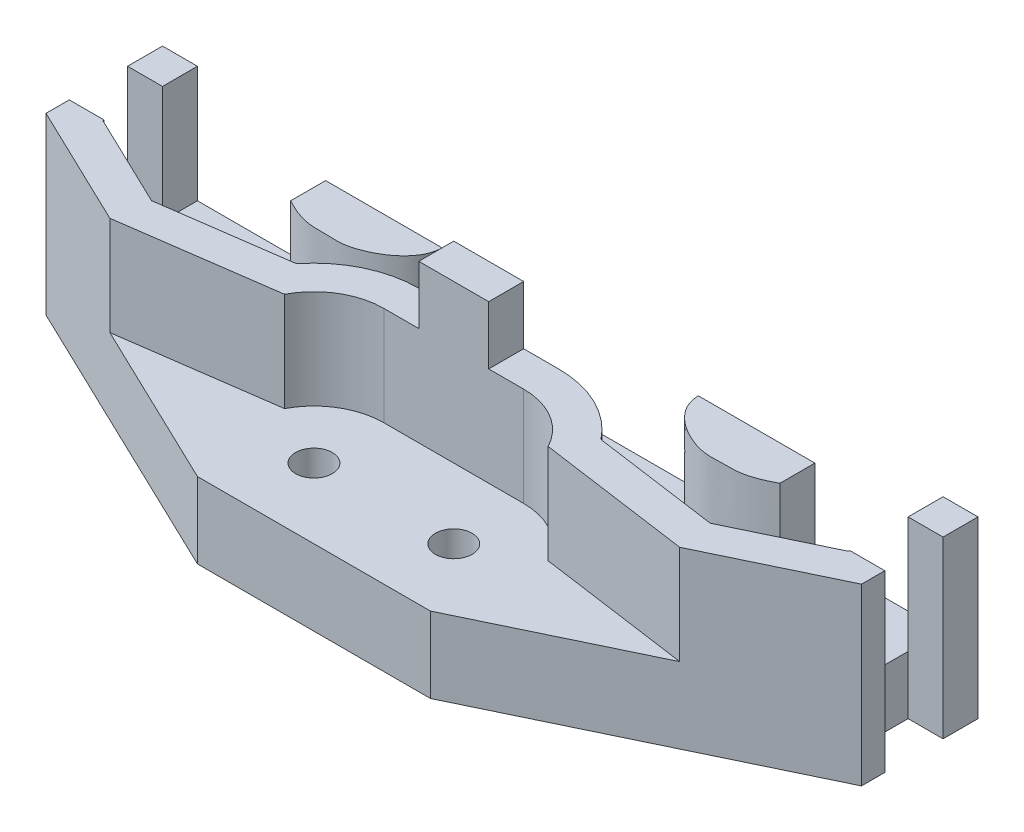
SolidWorks part; units mm, degrees
ref_plane "Front Plane" through (0, 0, 0) normal (0, 0, 1) x (1, 0, 0)
ref_plane "Top Plane" through (0, 0, 0) normal (0, 1, 0) x (1, 0, 0)
ref_plane "Right Plane" through (0, 0, 0) normal (1, 0, 0) x (0, 0, -1)
sketch "Sketch1" plane through (0, 0, 0) normal (0, 1, 0) x (1, 0, 0)
  line L0 (0, 0) -> (20, 0)
  line L1 (10, 0) -> (10, 12) construction
  line L2 (10, 12) -> (-25, 12) construction
  line L3 (0, 0) -> (-25, 12)
  line L4 (-25, 12) -> (-25, 22)
  line L5 (-25, 22) -> (45, 22)
  line L6 (45, 22) -> (45, 12)
  line L7 (45, 12) -> (20, 0)
  dimension "D1" = 35
  dimension "D2" = 20
  dimension "D3" = 12
  dimension "D4" = 70
  dimension "D5" = 10
  dimension "D6" = 10
extrude "Boss-Extrude1" add sketch "Sketch1" along normal blind 5
ref_plane "Plane1" through (10, 0, 0) normal (1, 0, 0) x (0, 0, -1)
sketch "Sketch2" plane through (0, 5, 0) normal (0, 1, 0) x (1, 0, 0)
  line L0 (10, 0) -> (10, 22) construction
  line L1 (0, 0) -> (20, 0) construction
  line L2 (45, 22) -> (-25, 22) construction
  circle A0 centre (4, 6) radius 1.575
  circle A1 centre (16, 6) radius 1.575
  dimension "D1" = 3.15
  dimension "D2" = 6
  dimension "D3" = 6
extrude "Cut-Extrude1" cut sketch "Sketch2" against normal blind 3
sketch "Sketch3" plane through (0, 5, 0) normal (0, 1, 0) x (1, 0, 0)
  line L0 (4, 6) -> (-8.7631, 4.2063) construction
  line L1 (-25, 12) -> (0, 0) construction
  line L2 (-8.7631, 4.2063) -> (-8.7631, 22) construction
  line L3 (45, 22) -> (-25, 22) construction
  line L4 (-2.3815, 5.1031) -> (-2.8686, 8.5691) construction
  line L5 (-2.8686, 8.5691) -> (4.0027, 9.5348) construction
  line L6 (-1.3131, 8.7877) -> (-14.4587, 6.9402)
  line L7 (10, 0) -> (10, 22) construction
  line L8 (0, 0) -> (20, 0) construction
  line L10 (-14.4587, 6.9402) -> (-25, 12)
  line L11 (-25, 12) -> (-25, 22)
  line L12 (-25, 22) -> (-22, 22)
  line L13 (-21.9703, 13.8734) -> (-25, 15.3277) construction
  line L14 (-21.9703, 13.8734) -> (-9.0961, 7.6939) construction
  line L15 (-19.7294, 9.4701) -> (-13.715, 22) construction
  line L17 (-3.069, 11.5704) -> (-13.9782, 10.0372)
  line L19 (-7.8859, 7.8639) -> (-9.8726, 22) construction
  line L21 (4, 12) -> (4, 15) construction
  line L30 (-22, 22) -> (-22, 13.8877)
  line L32 (0.4296, 9.0326) -> (0.012, 12.0034) construction
  line L33 (0.012, 12.0034) -> (-19.3407, 9.2836) construction
  line L34 (-22, 13.8877) -> (-13.9782, 10.0372)
  line L35 (4, 15) -> (16, 15)
  line L36 (4, 12) -> (16, 12)
  line L37 (21.3131, 8.7877) -> (34.4587, 6.9402)
  line L38 (34.4587, 6.9402) -> (45, 12)
  line L39 (45, 12) -> (45, 22)
  line L40 (45, 22) -> (42, 22)
  line L41 (42, 22) -> (42, 13.8877)
  line L42 (42, 13.8877) -> (33.9782, 10.0372)
  line L43 (23.069, 11.5704) -> (33.9782, 10.0372)
  arc A0 (-1.3131, 8.7877) -> (4, 12) centre (4, 6) cw
  arc A4 (4, 15) -> (-3.069, 11.5704) centre (4, 6) ccw
  arc A5 (21.3131, 8.7877) -> (16, 12) centre (16, 6) ccw
  arc A6 (16, 15) -> (23.069, 11.5704) centre (16, 6) cw
  point P34 (10, 12)
  point P35 (10, 12)
  point P36 (10, 15)
  point P52 (10, 15)
  dimension "D4" = 6
  dimension "D1" = 82
  dimension "D2" = 3.5
  dimension "D3" = 90
  dimension "D5" = 90
  dimension "D6" = 90
  dimension "D7" = 3
  dimension "D8" = 3
  dimension "D9" = 3
  dimension "D10" = 3
  dimension "D11" = 3
  dimension "D12" = 90
extrude "Boss-Extrude2" add sketch "Sketch3" along normal blind 10
sketch "Sketch9" plane through (0, 15, 0) normal (0, 1, 0) x (1, 0, 0)
  line L0 (10, 12) -> (10, 15) construction
  line L1 (4, 12) -> (16, 12) construction
  line L2 (16, 15) -> (4, 15) construction
  line L3 (16, 15) -> (4, 15) construction
  line L4 (7, 12) -> (13, 12)
  line L5 (7, 12) -> (7, 15)
  line L6 (7, 15) -> (13, 15)
  line L7 (13, 12) -> (13, 15)
  dimension "D1" = 3
  dimension "D2" = 3
extrude "Boss-Extrude3" add sketch "Sketch9" along normal blind 5
sketch "Sketch12" plane through (0, 15, 0) normal (0, 1, 0) x (1, 0, 0)
  line L0 (-25, 22) -> (-25, 12) construction
  line L1 (-25, 19) -> (-22, 19)
  line L2 (-25, 19) -> (-25, 14)
  line L3 (-25, 14) -> (-22, 14)
  line L4 (-22, 19) -> (-22, 14)
  line L5 (-22, 13.8877) -> (-22, 22) construction
  line L6 (-22, 22) -> (-25, 22) construction
  line L7 (10, 22) -> (10, 0) construction
  line L8 (42, 22) -> (-22, 22) construction
  line L9 (0, 0) -> (20, 0) construction
  line L10 (45, 14) -> (42, 14)
  line L11 (42, 19) -> (42, 14)
  line L12 (45, 19) -> (42, 19)
  line L13 (45, 19) -> (45, 14)
  dimension "D1" = 3
  dimension "D2" = 5
extrude "Cut-Extrude4" cut sketch "Sketch12" against normal blind 17
sketch "Sketch14" plane through (0, 5, 0) normal (0, 1, 0) x (1, 0, 0)
  line L0 (42, 22) -> (-22, 22) construction
  line L1 (21, 22) -> (31, 22)
  line L3 (26, 18) -> (28.2891, 18)
  line L4 (31, 22) -> (31, 19)
  line L5 (10, 22) -> (10, 0) construction
  line L6 (0, 0) -> (20, 0) construction
  line L7 (-0.7999, 18) -> (-10.7999, 18)
  line L8 (-11, 22) -> (-10.7999, 18)
  line L9 (-1, 22) -> (-11, 22)
  line L10 (-1, 22) -> (-0.7999, 18)
  line L13 (25.9305, 18) -> (23.1394, 18) construction
  line L14 (21, 19.713) -> (21, 24.3845) construction
  spline S0 degree 3 poles (21, 22) (21, 19.7457) (24.6092, 17.8685) (27.9309, 18.1418) (28.7395, 17.7851) (31, 19) knots 0 0 0 0 0.402282 0.502282 1 1 1 1
  line M17 (42, 22) -> (-22, 22)
  dimension "D1" = 4
  dimension "D2" = 10
  dimension "D3" = 3
  dimension "D4" = 21
  dimension "D5" = 5
extrude "Boss-Extrude5" add sketch "Sketch14" along normal offset from surface (7 mm away) 3 contours S0 L4 M17 region at (26.4101, 5, -20.2182) up to face at (28.8051, 15, -12.2313)
sketch "Sketch21" plane through (0, 0, 0) normal (0, -1, 0) x (1, 0, 0)
  line L0 (45, -22) -> (-25, -22) construction
  line L1 (14, -22) -> (6, -22)
  line L2 (14, -22) -> (14, -17)
  line L3 (14, -17) -> (6, -17)
  line L4 (6, -22) -> (6, -17)
  point P9 (10, -22)
  point P10 (10, -22)
  dimension "D1" = 8
  dimension "D2" = 5
extrude "Boss-Extrude9" add sketch "Sketch21" along normal blind 8
fillet "Fillet1" radius 3 1 edges at (10, 0, -17)
sketch "Sketch22" plane through (0, 0, -22) normal (0, 0, -1) x (-1, 0, 0)
  line L0 (-6, -8) -> (-14, -8) construction
  circle A0 centre (-10, -2) radius 1.5
  point P5 (-10, -8)
  dimension "D1" = 3
  dimension "D2" = 2
extrude "Cut-Extrude16" cut sketch "Sketch22" against normal up to next
sketch "Sketch24" plane through (0, 0, -22) normal (0, 0, -1) x (-1, 0, 0)
  line L6 (-6, -8) -> (-6, 0) construction
  line L7 (-14, -8) -> (-14, 0) construction
  line L8 (-14, -2) -> (-14, -13.3597)
  line L9 (-14, -13.3597) -> (-6, -13.3597)
  line L10 (-6, -13.3597) -> (-6, -2)
  arc A2 (-6, -2) -> (-14, -2) centre (-10, -2) cw
  circle A3 centre (-10, -2) radius 1.5 construction
extrude "Cut-Extrude11" cut sketch "Sketch24" against normal up to next
sketch "Sketch26" plane through (0, 0, -22) normal (0, 0, -1) x (-1, 0, 0)
  line L0 (-45, 0) -> (-14, 0) construction
  line L1 (-31, 0) -> (-21, 0)
  line L2 (-31, 0) -> (-31, -5)
  line L3 (-31, -5) -> (-21, -5)
  line L4 (-21, 0) -> (-21, -5)
  line L7 (-45, 15) -> (-45, 0) construction
  point P6 (-26, 0)
  dimension "D1" = 19
  dimension "D2" = 10
  dimension "D3" = 5
extrude "Boss-Extrude10" add sketch "Sketch26" against normal blind 10
sketch "Sketch29" plane through (31, 0, 0) normal (1, 0, 0) x (0, 0, -1)
  line L0 (12, -5) -> (22, -5) construction
  line L1 (13.5409, -5) -> (15.5485, -5) construction
  line L2 (10.4353, 0) -> (13.6364, 0) construction
  line L3 (22, 0) -> (22, -5) construction
  line L4 (12, 0) -> (12, -5) construction
  line L5 (12, -5) -> (14, -5)
  line L6 (12, 0) -> (12, -5)
  spline S0 degree 3 poles (14, -5) (13.4037, -5) (12.9336, -2.6301) (12.7861, 0) (12, 0) knots 0 0 0 0 0.556921 1 1 1 1
  dimension "D1" = 8
extrude "Cut-Extrude15" cut sketch "Sketch29" against normal up to next
sketch "Sketch27" plane through (0, 0, -22) normal (0, 0, -1) x (-1, 0, 0)
  line L0 (-31, -5) -> (-21, -5) construction
  line L2 (-21, 12) -> (-21, 5) construction
  circle A0 centre (-26, 0) radius 2.05
  point P5 (-26, -5)
  point P8 (-21, 8.5)
  dimension "D1" = 4.1
  dimension "D2" = 8.5
extrude "Cut-Extrude13" cut sketch "Sketch27" against normal blind 5
sketch "Sketch28" plane through (0, 0, -22) normal (0, 0, -1) x (-1, 0, 0)
  line L0 (-21, -5) -> (-21, 0) construction
  line L1 (-31, -5) -> (-21, -5) construction
  line L2 (-31, 0) -> (-31, -5) construction
  line L3 (-21, -5) -> (-21, 0)
  line L4 (-31, -5) -> (-21, -5)
  line L5 (-31, 0) -> (-31, -5)
  arc A0 (-31, 0) -> (-21, 0) centre (-26, 0) ccw
  line M19 (-31, 0) -> (-31, -5)
  line M20 (-31, -5) -> (-21, -5)
  line M21 (-21, -5) -> (-21, 0)
extrude "Cut-Extrude14" cut sketch "Sketch28" against normal up to next contours A0 L4 M21 | A0 M19 M20 region at (22.1168, -3.8832, -22) region at (29.8832, -3.8832, -22)
mirror "Mirror1" about plane through (10, 0, 0) normal (1, 0, 0) of "Cut-Extrude15", "Boss-Extrude10", "Cut-Extrude13", "Cut-Extrude14"
mirror "Mirror2" about plane through (10, 0, 0) normal (1, 0, 0) of "Boss-Extrude5"
fillet "Fillet2" radius 2 3 edges at (10.228, -0.5174, -15.6843) (10, -3.5, -17) (8.5, -2, -22)
fillet "Fillet3" radius 2 6 edges at (-11, 0, -17) (31, 0, -17) (6, 0, -18) (14, 0, -18)
sketch "Sketch31" plane through (0, 5, 0) normal (0, 1, 0) x (1, 0, 0)
  line L0 (-1.3131, 8.7877) -> (-14.4587, 6.9402)
  line L1 (-14.4587, 6.9402) -> (0, 0)
  line L2 (0, 0) -> (20, 0)
  line L3 (20, 0) -> (34.4587, 6.9402)
  line L4 (34.4587, 6.9402) -> (21.3131, 8.7877)
  line L5 (4, 12) -> (16, 12) construction
  line L6 (4, 12) -> (16, 12)
  arc A0 (21.3131, 8.7877) -> (16, 12) centre (16, 6) ccw
  arc A1 (4, 12) -> (-1.3131, 8.7877) centre (4, 6) ccw
  arc A2 (4, 12) -> (-1.3131, 8.7877) centre (4, 6) ccw construction
  circle A3 centre (4, 6) radius 1.575
  circle A4 centre (16, 6) radius 1.575
  dimension "D1" = 3.15
  dimension "D2" = 3.15
extrude "Boss-Extrude11" add sketch "Sketch31" along normal blind 1.5
